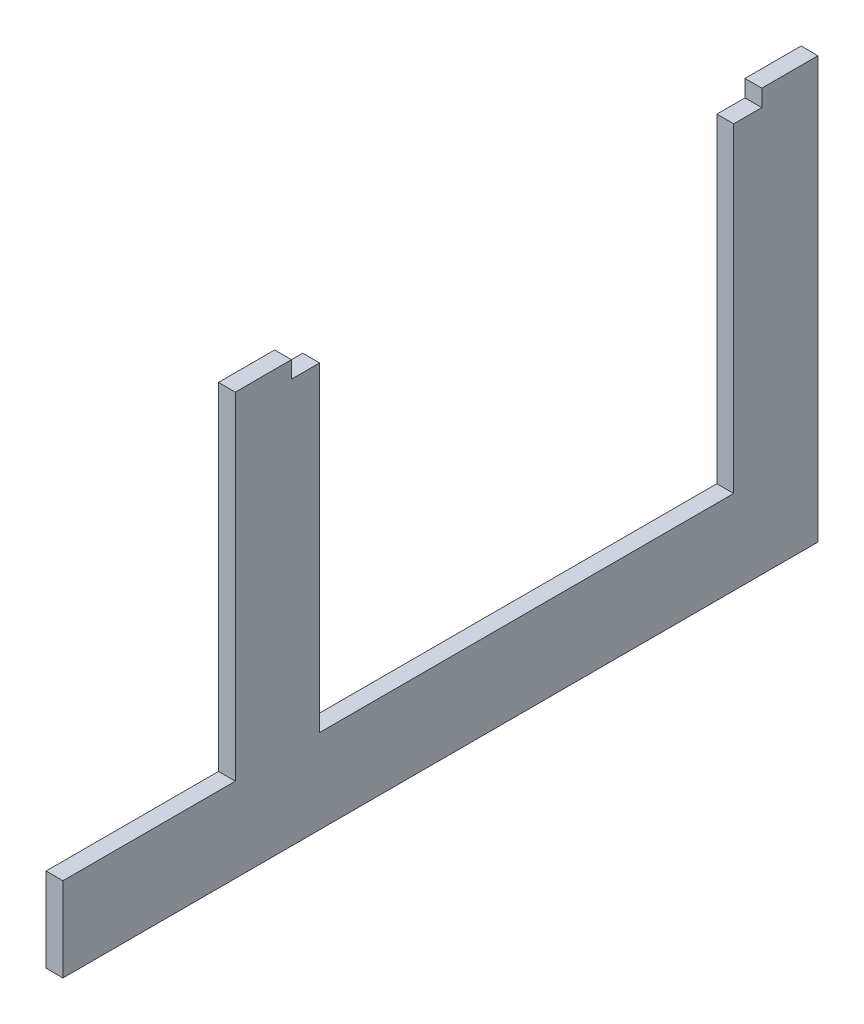
SolidWorks part; units mm, degrees
ref_plane "Front Plane" through (0, 0, 0) normal (0, 0, 1) x (1, 0, 0)
ref_plane "Top Plane" through (0, 0, 0) normal (0, 1, 0) x (1, 0, 0)
ref_plane "Right Plane" through (0, 0, 0) normal (1, 0, 0) x (0, 0, -1)
sketch "Sketch1" plane through (0, 0, 0) normal (0, 1, 0) x (1, 0, 0)
  line L0 (0, 0) -> (0, 103.7444) construction
  line L1 (-36.8722, 0) -> (36.8722, 0) construction
  line L2 (-36.8722, 0) -> (-36.8722, 103.7444)
  line L3 (-36.8722, 103.7444) -> (36.8722, 103.7444)
  line L4 (36.8722, 0) -> (36.8722, 103.7444)
  line L5 (36.8722, 103.7444) -> (36.8722, 0) construction
  line L6 (45.8722, 103.7444) -> (-45.8722, 103.7444) construction
  line L7 (21.0585, 67.686) -> (21.0585, 0)
  line L8 (-21.0585, 67.686) -> (-21.0585, 0)
  line L9 (-36.8722, 0) -> (-21.0585, 0)
  line L10 (21.0585, 0) -> (36.8722, 0)
  line L11 (31.8722, 103.7444) -> (31.8722, 88.7444) construction
  line L12 (34.8722, 103.7444) -> (34.8722, 88.7444) construction
  line L13 (31.8722, 93.7444) -> (34.8722, 93.7444) construction
  line L14 (31.8722, 10) -> (34.8722, 10) construction
  line L15 (31.8722, 88.7444) -> (34.8722, 88.7444) construction
  line L16 (31.8722, 15) -> (34.8722, 15) construction
  line L17 (31.8722, 15) -> (31.8722, 0) construction
  line L18 (34.8722, 15) -> (34.8722, 0) construction
  line L19 (33.3722, 93.7444) -> (33.3722, 88.7444) construction
  line L20 (33.3722, 15) -> (33.3722, 10) construction
  line L21 (34.8722, 100.7444) -> (-34.8722, 100.7444) construction
  line L22 (-34.8722, 100.7444) -> (-34.8722, 103.7444) construction
  line L23 (56.5, -60.7) -> (59.5, -60.7) construction
  arc A0 (21.0585, 67.686) -> (-21.0585, 67.686) centre (0, 67.686) ccw construction
  arc A1 (21.0585, 67.686) -> (-21.0585, 67.686) centre (0, 67.686) ccw
  circle A2 centre (28.9653, 80.8376) radius 1.75 construction
  circle A3 centre (-28.9653, 80.8376) radius 1.75 construction
  circle A4 centre (28.9653, 22.9069) radius 1.75 construction
  circle A5 centre (-28.9653, 22.9069) radius 1.75 construction
  circle A6 centre (28.9653, 80.8376) radius 1.75
  circle A7 centre (-28.9653, 80.8376) radius 1.75
  circle A8 centre (28.9653, 22.9069) radius 1.75
  circle A9 centre (-28.9653, 22.9069) radius 1.75
  dimension "D2" = 2
  dimension "D3" = 10
  dimension "D4" = 5
ref_plane "Plane1" through (34.8722, 0, 0) normal (1, 0, 0) x (0, 0, -1)
sketch "Sketch2" plane through (34.8722, 0, 0) normal (1, 0, 0) x (0, 0, -1)
  line L0 (103.7444, 3) -> (103.7444, -72)
  line L1 (103.7444, -72) -> (-30.7, -72)
  line L2 (0, -57) -> (0, 3)
  line L3 (0, 3) -> (10, 3)
  line L4 (10, 3) -> (10, 0)
  line L5 (10, 0) -> (15, 0)
  line L6 (15, 0) -> (15, -57)
  line L7 (15, -57) -> (88.7444, -57)
  line L8 (88.7444, -57) -> (88.7444, 0)
  line L9 (88.7444, 0) -> (93.7444, 0)
  line L10 (93.7444, 0) -> (93.7444, 3)
  line L11 (93.7444, 3) -> (103.7444, 3)
  line L12 (103.7444, 0) -> (88.7444, 0) construction
  line L13 (93.7444, 0) -> (103.7444, 0) construction
  line L14 (98.7444, 0) -> (98.7444, 3) construction
  line L15 (-30.7, -72) -> (-60.7, -72) construction
  line L16 (15, 0) -> (0, 0) construction
  line L17 (100.7444, 0) -> (103.7444, 0) construction
  line L18 (103.7444, -46) -> (0, -46) construction
  line L19 (-60.7, -72) -> (-60.7, -57) construction
  line L20 (-60.7, -45.3) -> (-60.7, 65.4444) construction
  line L21 (-30.7, -72) -> (-30.7, -57)
  line L22 (-30.7, -57) -> (-60.7, -57) construction
  line L23 (0, -57) -> (-30.7, -57)
  dimension "D1" = 46
  dimension "D2" = 72
  dimension "D3" = 15
  dimension "D4" = 30
extrude "Boss-Extrude1" add sketch "Sketch2" against normal up to vertex (3 mm away) up to point (31.8722, 0, -103.7444)
